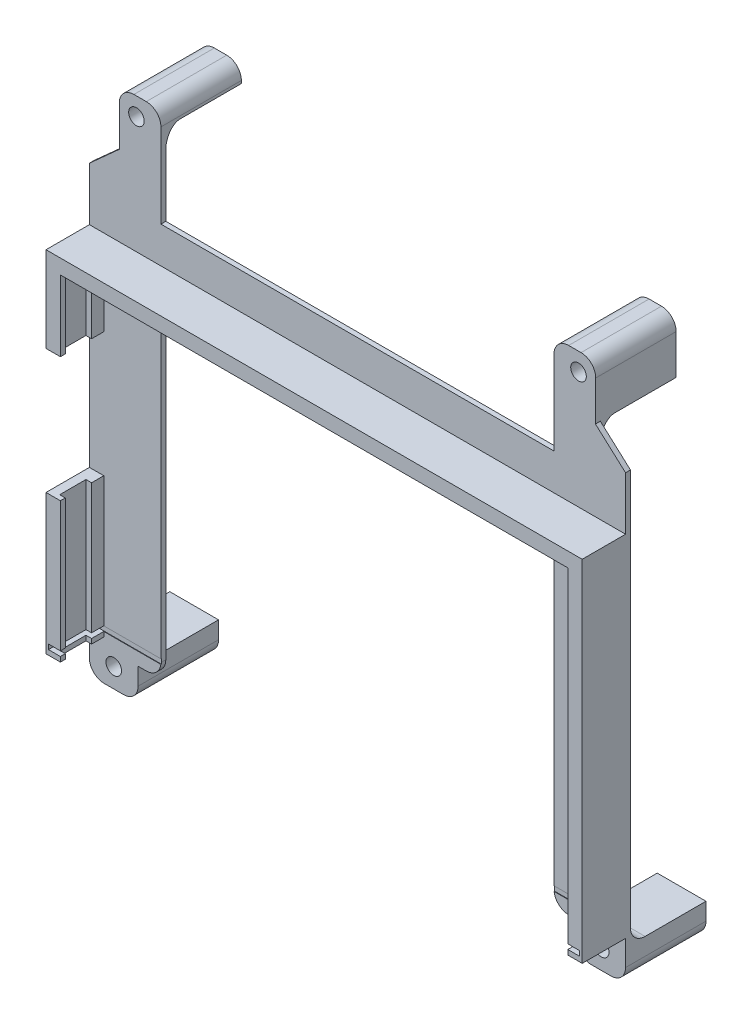
SolidWorks part; units mm, degrees
ref_plane "Front Plane" through (0, 0, 0) normal (1, 0, 0) x (0, 1, 0)
ref_plane "Top Plane" through (0, 0, 0) normal (0, 0, 1) x (0, 1, 0)
ref_plane "Right Plane" through (0, 0, 0) normal (0, 1, 0) x (-1, 0, 0)
sketch "Sketch1" plane through (0, 0, 0) normal (0, 0, 1) x (0, 1, 0)
  line L0 (-47.4715, -54.7542) -> (-54.0067, -54.7542)
  line L1 (-54.0067, -44.7542) -> (-54.0067, -54.7542)
  line L6 (-47.4715, -44.7542) -> (-54.0067, -44.7542)
  line L7 (-47.4715, -44.7542) -> (-47.4715, -54.7542)
  line L8 (42.478, -48.5761) -> (50.1367, -40.0774)
  line L9 (50.1367, -40.0774) -> (53.6912, -40.0774)
  line L10 (53.6912, -40.0774) -> (53.6912, -48.6408)
  line L11 (53.6912, -48.6408) -> (42.478, -48.5761)
  line L12 (53.6912, 49.1325) -> (42.478, 49.0678)
  line L13 (53.6912, 40.569) -> (53.6912, 49.1325)
  line L14 (50.1367, 40.569) -> (53.6912, 40.569)
  line L15 (42.478, 49.0678) -> (50.1367, 40.569)
  line L16 (-47.4715, 45.2458) -> (-47.4715, 55.2458)
  line L17 (-47.4715, 45.2458) -> (-54.0067, 45.2458)
  line L18 (-54.0067, 45.2458) -> (-54.0067, 55.2458)
  line L19 (-47.4715, 55.2458) -> (-54.0067, 55.2458)
  circle A0 centre (-50.0067, -49.7542) radius 1.6
  circle A1 centre (49.9933, -45.1018) radius 1.6
  circle A2 centre (49.9933, 45.5934) radius 1.6
  circle A3 centre (-50.0067, 50.2458) radius 1.6
extrude "Boss-Extrude1" add sketch "Sketch1" along normal blind 15.5
sketch "Sketch2" plane through (0, 0, 15.5) normal (0, 0, 1) x (1, 0, 0)
  line L0 (54.7542, -47.4715) -> (54.7542, -54.0067)
  line L1 (41.7542, -19.0067) -> (-42.2458, -19.0067) construction
  line L2 (-0.2458, -19.0067) -> (-0.2458, 62.4675) construction
  line L3 (-49.1325, 53.6912) -> (-49.0678, 42.478)
  line L4 (-40.569, 53.6912) -> (-49.1325, 53.6912)
  line L5 (44.7542, -54.0067) -> (54.7542, -54.0067)
  line L6 (44.7542, -47.4715) -> (44.7542, -54.0067)
  line L7 (40.0774, 53.6912) -> (40.0774, 33.4233)
  line L9 (-40.569, 53.6912) -> (-40.569, 33.4233)
  line L10 (-45.2458, -47.4715) -> (-40.569, -47.4715)
  line L11 (40.0774, 53.6912) -> (48.6408, 53.6912)
  line L12 (48.6408, 53.6912) -> (48.5761, 42.478)
  line L13 (-53.4458, -43.9132) -> (-53.4458, -44.8132)
  line L14 (-55.2458, -44.8132) -> (54.7542, -44.8132) construction
  line L15 (-45.2458, -47.4715) -> (-45.2458, -54.0067)
  line L16 (-45.2458, -54.0067) -> (-55.2458, -54.0067)
  line L17 (-55.2458, -47.4715) -> (-55.2458, -54.0067)
  line L18 (44.7542, -47.4715) -> (40.0774, -47.4715)
  line L19 (40.0774, -47.4715) -> (40.0774, 20.9868)
  line L20 (48.5761, 42.478) -> (54.7542, 36.9106)
  line L21 (54.7542, -47.4715) -> (54.7542, 36.9106)
  line L22 (40.0774, 20.9868) -> (-40.569, 20.9868)
  line L23 (40.0774, 33.4233) -> (-40.569, 33.4233)
  line L24 (-55.2458, -47.4715) -> (-55.2458, 36.9106)
  line L25 (-49.0678, 42.478) -> (-55.2458, 36.9106)
  line L26 (-40.569, -47.4715) -> (-40.569, 20.9868)
  line L27 (-52.317, -43.9132) -> (-52.317, -44.8132)
  line L28 (-49.1325, 53.6912) -> (-49.0678, 42.478)
  line L29 (-40.569, 53.6912) -> (-49.1325, 53.6912)
  line L31 (-53.4458, -43.9132) -> (52.9542, -43.9132) construction
  line L32 (52.9542, -43.9132) -> (52.9542, -44.8132)
  line L33 (-45.2458, -47.4715) -> (-45.2458, -54.0067)
  line L34 (-45.2458, -54.0067) -> (-55.2458, -54.0067)
  line L35 (-55.2458, -47.4715) -> (-55.2458, -54.0067)
  circle A0 centre (49.7542, -50.0067) radius 1.6
  circle A1 centre (45.1018, 49.9933) radius 1.6
  circle A2 centre (-45.5934, 49.9933) radius 1.6
  circle A3 centre (-50.2458, -50.0067) radius 1.6
  circle A4 centre (-45.5934, 49.9933) radius 1.6
  circle A5 centre (-50.2458, -50.0067) radius 1.6
  point P37 (-0.2458, 33.4233)
  point P38 (-0.2458, 20.9868)
  line M3 (48.5761, 42.478) -> (48.6408, 53.6912)
  line M4 (48.6408, 53.6912) -> (40.0774, 53.6912)
  line M5 (40.0774, 53.6912) -> (40.0774, 50.1367)
  line M6 (40.0774, 50.1367) -> (48.5761, 42.478)
  circle M7 centre (45.1018, 49.9933) radius 1.6
  dimension "D1" = 3.2
  dimension "D2" = 3.2
extrude "Boss-Extrude2" add sketch "Sketch2" along normal blind 1 contours L15 L26 L22 L19 L18 L6 L5 L0 L21 L20 L7 L23 L9 L4 L3 L25 L24 L17 L16 A2 A0 A3 M6 | M6 M3 M4 M5 M7 region at (53.2147, -50.7391, 15.5) region at (44.4212, 46.4122, 15.5)
sketch "Sketch3" plane through (0, 0, 16.5) normal (0, 0, 1) x (1, 0, 0)
  line L1 (-52.2958, 22.9868) -> (51.8042, 22.9868)
  line L2 (-52.2958, 22.9868) -> (-52.2958, 8.4399)
  line L3 (-52.2958, -42.8132) -> (-50.6497, -42.8132)
  line L4 (51.8042, 22.9868) -> (51.8042, -42.8132)
  line L5 (-52.2958, 22.9868) -> (51.8042, -42.8132) construction
  line L6 (-52.2958, -42.8132) -> (51.8042, 22.9868) construction
  line L20 (54.7542, 36.9106) -> (54.7542, -54.0067) construction
  line L21 (-55.2458, 25.9868) -> (54.7542, 25.9868)
  line L23 (40.0774, 20.9868) -> (-40.569, 20.9868) construction
  line L24 (-55.2458, 25.9868) -> (-55.2458, 8.4399)
  line L29 (-55.2458, -45.8132) -> (-52.2958, -45.8132)
  line L30 (54.7542, 25.9868) -> (54.7542, -45.8132)
  line L31 (-55.2458, 25.9868) -> (54.7542, -45.8132) construction
  line L32 (-55.2458, -45.8132) -> (54.7542, 25.9868) construction
  line L33 (-52.2958, -42.8132) -> (-52.2958, -45.8132)
  line L34 (51.8042, -42.8132) -> (51.8042, -45.8132)
  line L35 (51.8042, -45.8132) -> (54.7542, -45.8132)
  line L36 (50.1581, -42.8132) -> (51.8042, -42.8132)
  line L37 (-55.2458, 8.4399) -> (-52.2958, 8.4399)
  line L38 (-55.2458, -17.1408) -> (-52.2958, -17.1408)
  line L39 (-52.2958, -17.1408) -> (-52.2958, -42.8132)
  line L40 (-55.2458, -17.1408) -> (-55.2458, -45.8132)
  point P0 (-0.2458, -9.9132)
  point P5 (-0.2458, -9.9132)
  point P12 (-0.2458, -9.9132)
  point P20 (-0.2458, 20.9868)
  point P21 (-0.2458, -9.9132)
  line M14 (54.7542, -54.0067) -> (54.7542, 36.9106)
  line M24 (-55.2458, 36.9106) -> (-55.2458, -54.0067)
  dimension "D1" = 104.1
  dimension "D2" = 65.8
  dimension "D3" = 2
  dimension "D4" = 3
extrude "Boss-Extrude3" add sketch "Sketch3" along normal blind 2.5 contours L34 L35 L21 L29 L33 L2 L1 L4 M14 M24 | L33 L29 L40 L38 L39 region at (-53.6094, 15.7133, 16.5)
sketch "Sketch4" plane through (0, 0, 19) normal (0, 0, 1) x (1, 0, 0)
  line L0 (-0.2458, 22.9868) -> (-0.2458, -59.386) construction
  line L1 (-52.2958, 22.9868) -> (51.8042, 22.9868) construction
  line L2 (-55.2458, -45.8132) -> (54.7542, -45.8132) construction
  line L3 (-55.2458, 25.9868) -> (54.7542, 25.9868)
  line L4 (-55.2458, 25.9868) -> (-55.2458, 8.4399)
  line L5 (-55.2458, -45.8132) -> (-53.4458, -45.8132)
  line L6 (54.7542, 25.9868) -> (54.7542, -45.8132)
  line L7 (-55.2458, 25.9868) -> (54.7542, -45.8132) construction
  line L8 (-55.2458, -45.8132) -> (54.7542, 25.9868) construction
  line L9 (-53.4458, 24.0868) -> (52.9542, 24.0868)
  line L10 (-53.4458, 24.0868) -> (-53.4458, 8.4399)
  line L12 (52.9542, 24.0868) -> (52.9542, -43.9132)
  line L13 (-53.4458, 24.0868) -> (52.9542, -43.9132) construction
  line L14 (-53.4458, -43.9132) -> (52.9542, 24.0868) construction
  line L15 (-53.4458, -43.9132) -> (-53.4458, -45.8132)
  line L16 (52.9542, -43.9132) -> (52.9542, -45.8132)
  line L17 (52.9542, -45.8132) -> (54.7542, -45.8132)
  line L18 (-55.2458, 8.4399) -> (-53.4458, 8.4399)
  line L19 (-55.2458, 8.4399) -> (-52.2958, 8.4399) construction
  line L20 (-55.2458, -17.1408) -> (-53.4458, -17.1408)
  line L21 (-55.2458, -17.1408) -> (-52.2958, -17.1408) construction
  line L22 (-55.2458, -17.1408) -> (-55.2458, -45.8132)
  line L23 (-53.4458, -17.1408) -> (-53.4458, -43.9132)
  line L24 (-55.2458, -43.8132) -> (54.7542, -43.8132) construction
  point P4 (-0.2458, -9.9132)
  point P13 (-0.2458, -9.9132)
  dimension "D1" = 106.4
  dimension "D2" = 68
  dimension "D3" = 67.9
extrude "Boss-Extrude4" add sketch "Sketch4" along normal blind 5.4
sketch "Sketch5" plane through (0, 0, 24.4) normal (0, 0, 1) x (1, 0, 0)
  line L0 (-55.2458, 8.4399) -> (-52.2958, 8.4399)
  line L1 (-52.2958, 22.9868) -> (51.8042, 22.9868)
  line L2 (-52.2958, 22.9868) -> (-52.2958, 8.4399)
  line L4 (51.8042, 22.9868) -> (51.8042, -45.8132)
  line L5 (-55.2458, 25.9868) -> (54.7542, 25.9868)
  line L6 (-55.2458, 25.9868) -> (-55.2458, 8.4399)
  line L7 (-55.2458, -45.8132) -> (-52.2958, -45.8132)
  line L8 (54.7542, 25.9868) -> (54.7542, -45.8132)
  line L9 (-55.2458, -17.1408) -> (-52.2958, -17.1408)
  line L10 (51.8042, -45.8132) -> (54.7542, -45.8132)
  line L11 (-52.2958, -17.1408) -> (-52.2958, -45.8132)
  line L12 (-55.2458, -17.1408) -> (-55.2458, -45.8132)
extrude "Boss-Extrude5" add sketch "Sketch5" along normal blind 1
sketch "Sketch7" plane through (0, 0, 25.4) normal (0, 0, 1) x (1, 0, 0)
  line L0 (-54.7458, -43.8132) -> (54.2542, -43.8132)
  line L1 (54.2542, -43.8132) -> (54.2542, -44.8132)
  line L2 (54.2542, -44.8132) -> (-54.7458, -44.8132)
  line L3 (-54.7458, -44.8132) -> (-54.7458, -43.8132)
  line L4 (51.8042, -45.8132) -> (54.7542, -45.8132) construction
  line L5 (54.7542, -45.8132) -> (54.7542, 25.9868) construction
  line L6 (-55.2458, -17.1408) -> (-55.2458, -45.8132) construction
  dimension "D1" = 1
  dimension "D2" = 1
  dimension "D3" = 0.5
  dimension "D4" = 0.5
extrude "Cut-Extrude1" cut sketch "Sketch7" against normal blind 9
fillet "Fillet1" radius 3 10 edges at (48.6408, 53.6912, 8.25) (-49.1325, 53.6912, 8.25) (-40.569, -47.4715, 16) (-55.2458, -54.0067, 8.25) (-45.2458, -54.0067, 8.25) (40.0774, -47.4715, 16) (44.7542, -54.0067, 8.25) (54.7542, -54.0067, 8.25) (40.0774, 53.6912, 8.25) (-40.569, 53.6912, 8.25)
fillet "Fillet2" radius 3 4 edges at (-50.2458, -47.4715, 15.5) (-44.8184, 46.3073, 15.5) (44.3268, 46.3073, 15.5) (49.7542, -47.4715, 15.5)
